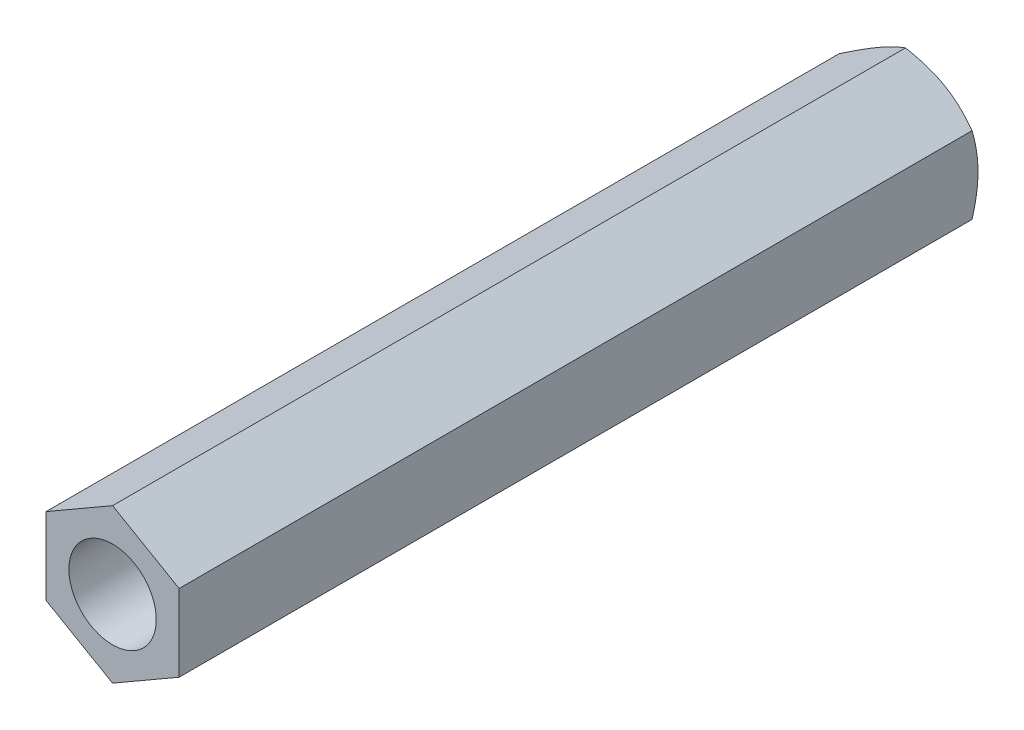
SolidWorks part; units mm, degrees
ref_plane "Front Plane" through (0, 0, 0) normal (0, 0, 1) x (1, 0, 0)
ref_plane "Top Plane" through (0, 0, 0) normal (0, 1, 0) x (1, 0, 0)
ref_plane "Right Plane" through (0, 0, 0) normal (1, 0, 0) x (0, 0, -1)
sketch "Sketch3" plane through (0, 0, 0) normal (1, 0, 0) x (0, 0, -1)
  line L0 (-19.05, 0) -> (19.05, 0) construction
  line L1 (0, 3.175) -> (0, -3.175) construction
  line L2 (-19.05, 2.0828) -> (-19.05, -2.0828) construction
  point P2 (9.525, 0)
  point P3 (-9.525, 0)
  dimension "Length" = 38.1
  dimension "Min Thread Length" = 9.525
  dimension "D1" = 9.525
  dimension "Thread Dia" = 4.1656
  dimension "Hex" = 6.35
sketch "Sketch1" plane through (0, 0, 0) normal (0, 0, 1) x (1, 0, 0)
  line L1 (0, 3.6662) -> (-3.175, 1.8331)
  line L2 (-3.175, 1.8331) -> (-3.175, -1.8331)
  line L3 (-3.175, -1.8331) -> (0, -3.6662)
  line L4 (0, -3.6662) -> (3.175, -1.8331)
  line L5 (3.175, -1.8331) -> (3.175, 1.8331)
  line L6 (3.175, 1.8331) -> (0, 3.6662)
  circle A0 centre (0, 0) radius 3.175 construction
  circle A1 centre (0, 0) radius 2.0828
extrude "Extrude1" add sketch "Sketch1" along normal up to vertex (19.05 mm away) and the other way up to vertex (19.05 mm away) up to point (0, 0, 19.05) other way up to point (0, 0, -19.05)
sketch "Sketch7" plane through (0, 0, -19.05) normal (0, 0, -1) x (-1, 0, 0)
  circle A2 centre (0, 0) radius 2.1336
  circle A3 centre (0, 0) radius 2.1336
  dimension "D1" = 0.0508
extrude "Extrude3" cut sketch "Sketch7" against normal through all draft 43
sketch "Sketch8" plane through (0, 0, -19.05) normal (0, 0, -1) x (-1, 0, 0)
  circle A0 centre (0, 0) radius 3.175 construction
  circle A1 centre (0, 0) radius 3.175
extrude "Extrude4" cut sketch "Sketch8" against normal through all draft 60 flip side to cut
ref_axis "Axis1" through (0, 0, -20.955) along (0, 0, 1)
equation "\"D1@Sketch3\" = \"Min Thread Length@Sketch3\""
